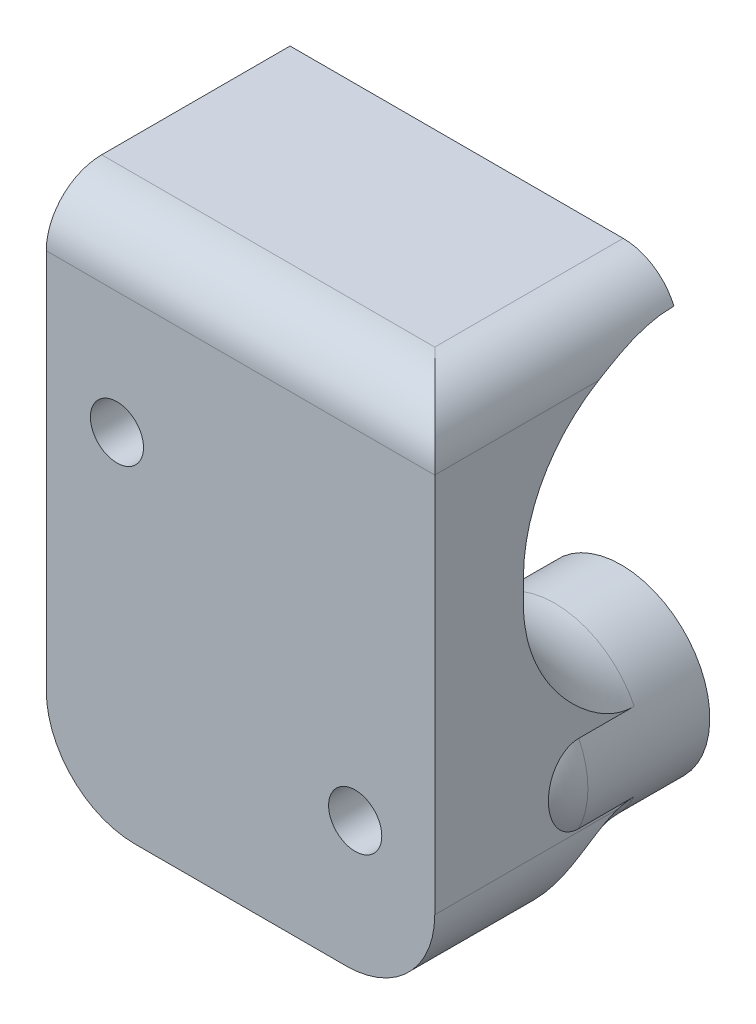
SolidWorks part; units mm, degrees
ref_plane "Front" through (0, 0, 0) normal (0, 0, 1) x (1, 0, 0)
ref_plane "Top" through (0, 0, 0) normal (0, 1, 0) x (1, 0, 0)
ref_plane "Right" through (0, 0, 0) normal (1, 0, 0) x (0, 0, -1)
sketch "Эскиз1" plane through (0, 0, 0) normal (0, 0, 1) x (1, 0, 0)
  line L0 (2.2009, 1.2487) -> (19.7294, 1.2487)
  line L1 (2.2009, 1.2487) -> (2.2009, 24.9297)
  line L2 (2.2009, 24.9297) -> (19.7294, 24.9297)
  line L3 (19.7294, 1.2487) -> (19.7294, 24.9297)
  circle A0 centre (16.1394, 7.1297) radius 1.2
  circle A1 centre (5.3909, 16.9297) radius 1.1977
  dimension "D1" = 3.19
  dimension "D2" = 17.5285
  dimension "D3" = 3.59
extrude "Бобышка-Вытянуть1" add sketch "Эскиз1" along normal blind 4
sketch "Эскиз2" plane through (0, 0, 0) normal (0, 0, -1) x (-1, 0, 0)
  line L0 (-2.2009, 24.9297) -> (-2.2009, 1.2487) construction
  line L1 (-19.7294, 24.9297) -> (-2.2009, 24.9297)
  line L2 (-19.7294, 24.9297) -> (-19.7294, 23.4297)
  line L3 (-19.7294, 23.4297) -> (-2.2009, 23.4297)
  line L4 (-2.2009, 24.9297) -> (-2.2009, 23.4297)
  dimension "D1" = 1.5
extrude "Бобышка-Вытянуть2" add sketch "Эскиз2" along normal blind 7
fillet "Скругление1" radius 4 2 edges at (2.2009, 1.2487, 2) (19.7294, 1.2487, 2)
sketch "Эскиз3" plane through (0, 0, 0) normal (0, 0, -1) x (-1, 0, 0)
  circle A0 centre (-16.1394, 7.1297) radius 1.1977
  circle A1 centre (-16.1394, 7.1297) radius 4
extrude "Бобышка-Вытянуть3" add sketch "Эскиз3" along normal blind 8
fillet "Скругление2" radius 5 1 edges at (12.1394, 7.1297, 0)
fillet "Скругление3" radius 7 1 edges at (10.9651, 23.4297, 0)
fillet "Скругление4" radius 2.5 1 edges at (20.1394, 7.1297, 0)
fillet "Скругление5" radius 2.5 2 edges at (10.9651, 24.9297, 4) (19.7294, 24.9297, -1.5)
